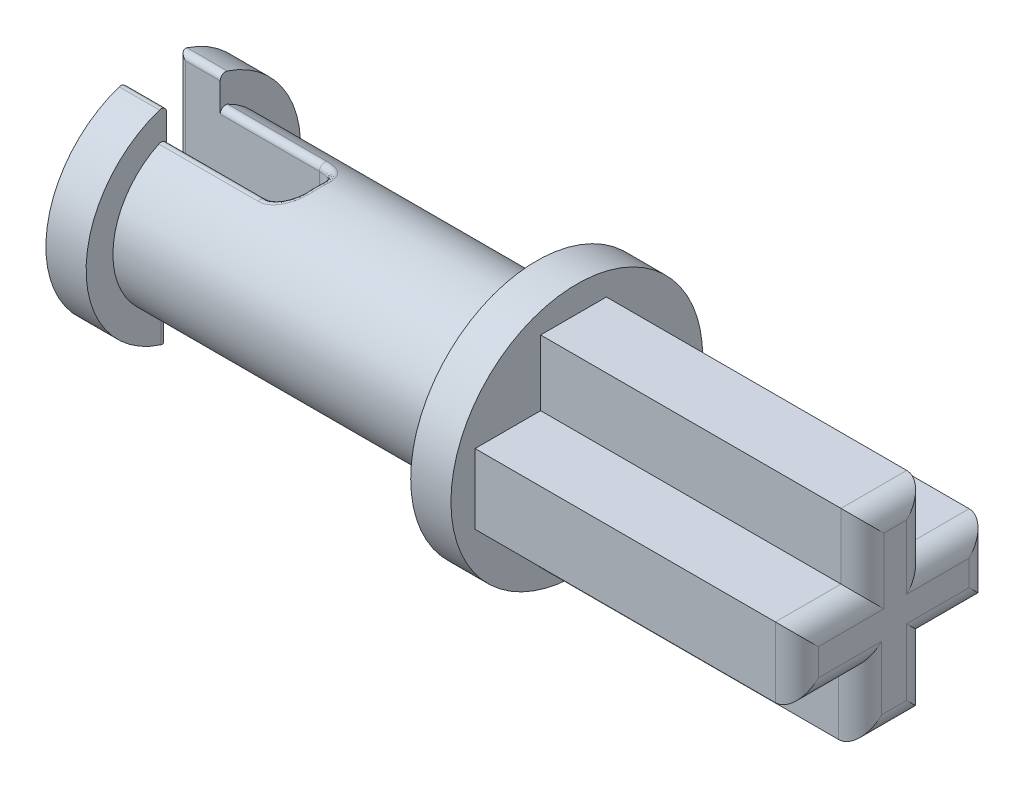
SolidWorks part; units mm, degrees
ref_plane "Front Plane" through (0, 0, 0) normal (0, 0, 1) x (1, 0, 0)
ref_plane "Top Plane" through (0, 0, 0) normal (0, 1, 0) x (1, 0, 0)
ref_plane "Right Plane" through (0, 0, 0) normal (1, 0, 0) x (0, 0, -1)
sketch "CircularBase" plane through (0, 0, 0) normal (0, 0, 1) x (1, 0, 0)
  line L0 (-5.0594, 0) -> (5.9, 0) construction
  line L1 (0, 0) -> (0, 0.5)
  line L2 (0, 0.5) -> (-2, 0.5)
  line L3 (-2, 0.5) -> (-2, 2)
  line L4 (-2, 2) -> (-1.25, 2)
  line L5 (-1.25, 2) -> (-1.25, 1.5)
  line L6 (-1.25, 1.5) -> (5.15, 1.5)
  line L7 (5.15, 1.5) -> (5.15, 2.3473)
  line L9 (5.9, 2.3473) -> (5.9, 0)
  line L11 (0, 0) -> (5.9, 0)
  line L12 (7.0797, 0) -> (14.1483, 0) construction
  line L13 (5.15, 2.3473) -> (5.9, 2.3473)
  dimension "D2" = 0.75
  dimension "D4" = 0.5
  dimension "D5" = 1.5
  dimension "D6" = 0.5
  dimension "D8" = 2
  dimension "D9" = 5.9
revolve "CircularBaseRevolve" add sketch "CircularBase" angle 360 about L12
ref_plane "BasePlane" through (-2, 0, 0) normal (-1, 0, 0) x (0, 0, 1)
sketch "NotchCutSketc" plane through (-2, 0, 0) normal (-1, 0, 0) x (0, 0, 1)
  line L0 (0, 2) -> (0, -2) construction
  line L1 (-0.5, 0) -> (-0.5, 1.9365)
  line L2 (-0.5, 1.9365) -> (0.5, 1.9365)
  line L3 (-0.5, 0) -> (-0.5, -1.9365)
  line L4 (-0.5, -1.9365) -> (0.5, -1.9365)
  line L5 (0.5, 0) -> (0.5, -1.9365)
  line L6 (0.5, 0) -> (0.5, 1.9365)
  circle A0 centre (0, 0) radius 2 construction
  circle A1 centre (0, 0) radius 0.5 construction
  circle A2 centre (0, 0) radius 0.5 construction
  point P15 (0, -1.9365)
  point P17 (0, 1.9365)
extrude "NotchCut" cut sketch "NotchCutSketc" against normal blind 3
fillet "InsideNotchFillet1" radius 0.4 1 edges at (1, 0, -0.5) type face fillet first side face at (-0.875, 0, -0.5) second side face at (1, 0, 0)
fillet "InsideNotchFillet2" radius 0.4 1 edges at (1, 0, 0.5) type face fillet first side face at (-0.875, 0, 0.5) second side face at (1, 0, 0.2021)
fillet "OutsideNotchFillet" radius 0.1 16 edges at (-2, 0, 0.5) (-2, 0, -0.5) (-0.325, -1.4142, -0.5) (0.915, -1.4594, -0.3465) (1, -1.5, 0) (0.8413, -1.4403, 0.419) (-0.325, 1.4142, 0.5) (0.915, 1.4594, 0.3465) (1, 1.5, 0) (0.8413, 1.4403, -0.419) (-1.625, 1.9365, 0.5) (-1.625, 1.9365, -0.5) (-1.625, -1.9365, -0.5) (-0.325, -1.4142, 0.5) (-0.325, 1.4142, -0.5) (-1.25, -1.6754, 0.5)
ref_plane "TopBasePlane" through (5.9, 0, 0) normal (1, 0, 0) x (0, 0, -1)
sketch "TopCircularBaseExtrudeSketch" plane through (5.9, 0, 0) normal (1, 0, 0) x (0, 0, -1)
  line L16 (-1.8975, -0.6644) -> (-1.8975, 0.6397)
  line L17 (-1.8975, 0.6397) -> (-0.6748, 0.6397)
  line L18 (0.5517, 1.8623) -> (-0.6748, 1.8623)
  line L19 (-0.6748, 1.8623) -> (-0.6748, 0.6397)
  line L20 (1.7152, -0.613) -> (1.7152, 0.6617)
  line L21 (1.7152, 0.6617) -> (0.5517, 0.6617)
  line L22 (0.5517, 1.8623) -> (0.5517, 0.6617)
  line L23 (1.7152, -0.613) -> (0.547, -0.613)
  line L24 (0.547, -1.851) -> (0.547, -0.613)
  line L25 (-1.8975, -0.6644) -> (-0.7166, -0.6644)
  line L26 (-0.7166, -1.851) -> (-0.7166, -0.6644)
  line L27 (0.547, -1.851) -> (-0.7166, -1.851)
  point P16 (1.7152, 0.0244)
extrude "TopCircularBaseExtrude" add sketch "TopCircularBaseExtrudeSketch" along normal blind 6
fillet "TopCircularBaseFillet" radius 0.4 12 edges at (11.9, 1.251, 0.6748) (11.9, 1.262, -0.5517) (11.9, 0.6397, 1.2862) (11.9, 0.6617, -1.1335) (11.9, 0.0244, -1.7152) (11.9, -0.613, -1.1311) (11.9, -1.232, -0.547) (11.9, -1.851, 0.0848) (11.9, -0.0124, 1.8975) (11.9, 1.8623, 0.0616) (11.9, -0.6644, 1.3071) (11.9, -1.2577, 0.7166)
fillet "TopCircularbaseSideFillet" [suppressed] radius 0.1
ref_plane "Plane1" [suppressed] through (0, -2.007, 0) normal (0, -1, 0) x (-1, 0, 0)
sketch "CircularTipSketch" [suppressed] plane through (0, -2.007, 0) normal (0, -1, 0) x (-1, 0, 0)
  line L0 (-6, 2.0033) -> (-6, -2.0033)
  line L1 (-6, -2.0033) -> (-6, -2.5355)
  line L2 (-6, -2.5355) -> (2.115, -2.5355)
  line L3 (2.115, -2.5355) -> (1.9623, 2.8509)
  line L4 (1.9623, 2.8509) -> (-6, 2.7898)
  line L5 (-6, 2.7898) -> (-6, 2.0033)
extrude "CircularTip" [suppressed] cut sketch "CircularTipSketch" against normal through all
ref_plane "Plane2" [suppressed] through (6, 0, 0) normal (-1, 0, 0) x (0, 0, 1)
mirror "Mirror2" [suppressed]
ref_plane "Plane3" [suppressed] through (0, 2.007, 0) normal (0, 1, 0) x (1, 0, 0)
sketch "BaseCutSketch" [suppressed] plane through (0, 2.007, 0) normal (0, 1, 0) x (1, 0, 0)
  line L0 (5.15, 2.5558) -> (5.15, -2.5)
  line L1 (5.15, -2.5) -> (-2.0426, -2.5)
  line L2 (-2.0426, -2.5) -> (-2.0426, 2.5558)
  line L3 (-2.0426, 2.5558) -> (5.15, 2.5558)
extrude "BaseCut" [suppressed] cut sketch "BaseCutSketch" against normal through all contours L3 L2 L1 L0
ref_plane "Plane4" [suppressed] through (13.8, 0, 0) normal (1, 0, 0) x (0, 0, -1)
sketch "NotchCutSketch" [suppressed] plane through (0, 0, 0) normal (0, 1, 0) x (1, 0, 0)
  line L7 (7.7505, 3.747) -> (7.7505, 0)
  line L14 (7.7505, 0) -> (10.818, 0) construction
  line L19 (7.7505, 0) -> (5.15, 0)
  line L20 (5.15, 2.5) -> (5.15, -2.5) construction
  line L21 (5.15, 0) -> (5.15, 4)
  line L22 (5.15, 4) -> (6.4505, 4)
  line L23 (6.4505, 4) -> (6.4505, 3.747)
  line L24 (6.4505, 3.747) -> (7.7505, 3.747)
  point P16 (7.1, 2.25)
  dimension "D1" = 1.3
  dimension "D2" = 4
revolve "CircularEvolveWithNotch" [suppressed] add sketch "NotchCutSketch" angle 360 about L14
ref_plane "Plane5" [suppressed] through (5.15, 0, 0) normal (-1, 0, 0) x (0, 0, 1)
sketch "CrossHoleCutSketch" [suppressed] plane through (5.15, 0, 0) normal (-1, 0, 0) x (0, 0, 1)
  line L0 (-0.8429, 0.8584) -> (-0.8429, 1.9149)
  line L1 (-0.6429, 2.1149) -> (0.6506, 2.1149)
  line L2 (0.8506, 1.9149) -> (0.8506, 0.8584)
  line L3 (0.8506, 0.8584) -> (1.9071, 0.8584)
  line L4 (-1.8994, 0.8584) -> (-0.8429, 0.8584)
  line L5 (-0.8429, -0.8427) -> (-1.8994, -0.8427)
  line L6 (-0.8429, -0.8427) -> (-0.8429, -1.8992)
  line L7 (-0.6429, -2.0992) -> (0.6506, -2.0992)
  line L8 (0.8506, -1.8992) -> (0.8506, -0.8427)
  line L9 (0.8506, -0.8427) -> (1.9071, -0.8427)
  line L10 (2.1071, -0.6427) -> (2.1071, 0.6584)
  line L11 (-2.0994, -0.6427) -> (-2.0994, 0.6584)
  arc A0 (-0.8429, 1.9149) -> (-0.6429, 2.1149) centre (-0.6429, 1.9149) cw
  arc A1 (0.8506, 1.9149) -> (0.6506, 2.1149) centre (0.6506, 1.9149) ccw
  arc A2 (1.9071, 0.8584) -> (2.1071, 0.6584) centre (1.9071, 0.6584) cw
  arc A3 (1.9071, -0.8427) -> (2.1071, -0.6427) centre (1.9071, -0.6427) ccw
  arc A4 (0.8506, -1.8992) -> (0.6506, -2.0992) centre (0.6506, -1.8992) cw
  arc A5 (-0.6429, -2.0992) -> (-0.8429, -1.8992) centre (-0.6429, -1.8992) cw
  arc A6 (-1.8994, -0.8427) -> (-2.0994, -0.6427) centre (-1.8994, -0.6427) cw
  arc A7 (-1.8994, 0.8584) -> (-2.0994, 0.6584) centre (-1.8994, 0.6584) ccw
extrude "CrossHoleCut" [suppressed] cut sketch "CrossHoleCutSketch" against normal through all
ref_plane "Plane11" [suppressed] through (7.7505, 0, 0) normal (1, 0, 0) x (0, 0, -1)
sketch "Sketch16" [suppressed] plane through (7.7505, 0, 0) normal (1, 0, 0) x (0, 0, -1)
  line L1 (0.8429, 0.8584) -> (0.8429, 1.9149)
  line L3 (-0.8506, 0.8584) -> (-1.9071, 0.8584)
  line L4 (-2.1071, 0.6584) -> (-2.1071, -0.6427)
  line L5 (-1.9071, -0.8427) -> (-0.8506, -0.8427)
  line L6 (-0.8506, -0.8427) -> (-0.8506, -1.8992)
  line L7 (0.8429, -1.8992) -> (0.8429, -0.8427)
  line L8 (0.8429, -0.8427) -> (1.8994, -0.8427)
  line L9 (2.0994, -0.6427) -> (2.0994, 0.7075)
  line L10 (0.8429, 0.8584) -> (1.8994, 0.8584)
  line L11 (-0.6506, -2.0992) -> (0.6429, -2.0992)
  line L12 (-0.8506, 0.8584) -> (-0.8506, 1.9149)
  line L13 (-0.6506, 2.1149) -> (0.6429, 2.1149)
  circle A0 centre (0, 0) radius 4
  arc A1 (-1.9071, -0.8427) -> (-2.1071, -0.6427) centre (-1.9071, -0.6427) cw
  arc A2 (-2.1071, 0.6584) -> (-1.9071, 0.8584) centre (-1.9071, 0.6584) cw
  arc A6 (1.8994, 0.8584) -> (2.0994, 0.7075) centre (1.8994, 0.6504) cw
  arc A7 (2.0994, -0.6427) -> (1.8994, -0.8427) centre (1.8994, -0.6427) cw
  arc A8 (0.8429, -1.8992) -> (0.6429, -2.0992) centre (0.6429, -1.8992) cw
  arc A9 (-0.8506, -1.8992) -> (-0.6506, -2.0992) centre (-0.6506, -1.8992) ccw
  arc A10 (-0.8506, 1.9149) -> (-0.6506, 2.1149) centre (-0.6506, 1.9149) cw
  arc A11 (0.8429, 1.9149) -> (0.6429, 2.1149) centre (0.6429, 1.9149) ccw
extrude "CircularCrossHolwCircle" [suppressed] add sketch "Sketch16" along normal blind 1.25
fillet "EdgesFillet" [suppressed] radius 0.1
fillet "Fillet2" [suppressed] radius 0.1
ref_plane "Plane6" [suppressed] through (0, 0, -2.0033) normal (0, 0, -1) x (-1, 0, 0)
sketch "Sketch1" [suppressed] plane through (0, 0, -2.0033) normal (0, 0, -1) x (-1, 0, 0)
  line L0 (-5.9, 2.5) -> (-5.9, -2.5)
  line L1 (-5.9, 2.5) -> (-5.9, -2.5) construction
  line L2 (-5.9, -2.5) -> (-13.8486, -2.5)
  line L3 (-13.8486, -2.5) -> (-13.8486, 2.5)
  line L4 (-13.8486, 2.5) -> (-5.9, 2.5)
extrude "RemovedMaterial" [suppressed] cut sketch "Sketch1" against normal through all
sketch "Sketch2" [suppressed] plane through (0, 0, -2.0033) normal (0, 0, -1) x (-1, 0, 0)
  line L1 (-11.5273, 0) -> (-12.3621, 0) construction
  line L2 (-5.15, 4.2) -> (-5.15, 0.25)
  line L3 (-5.15, 4.2) -> (-8.341, 4.2)
  line L4 (-8.341, 1.2482) -> (-11.5214, 1.2482)
  line L6 (-11.5214, 1.2482) -> (-11.5214, 0.25)
  line L8 (-8.341, 4.2) -> (-8.341, 1.2482)
  line L10 (-5.15, -2.5) -> (-5.15, 2.5) construction
  line L11 (-5.15, 0.25) -> (-11.5214, 0.25)
  dimension "D1" = 3.95
revolve "Revolve2" [suppressed] add sketch "Sketch2" angle 360 about L1
ref_plane "Plane8" [suppressed] through (5.9, 0, 0) normal (1, 0, 0) x (0, 0, -1)
sketch "Sketch13" [suppressed] plane through (5.9, 0, 0) normal (1, 0, 0) x (0, 0, -1)
  arc A0 (-1.8412, 1.6911) -> (-1.8412, -1.6911) centre (0, 0) ccw
  arc A2 (-1.8412, 1.6911) -> (-1.8412, -1.6911) centre (2.0033, 0) ccw
  dimension "D1" = 2.5
extrude "RemovedMaterial2" [suppressed] cut sketch "Sketch13" against normal through all
sketch "Sketch14" [suppressed] plane through (5.9, 0, 0) normal (1, 0, 0) x (0, 0, -1)
  line L0 (2.0033, -0.25) -> (2.0033, 0.25) construction
  circle A0 centre (2.0033, 0) radius 0.2516
ref_plane "ShellPlane" [suppressed] through (5.15, 0, 0) normal (-1, 0, 0) x (0, 0, 1)
sketch "ShellSketch" [suppressed] plane through (5.15, 0, 0) normal (-1, 0, 0) x (0, 0, 1)
  circle A0 centre (-2.0033, 0) radius 1.9017
extrude "ShellFeature" [suppressed] cut sketch "ShellSketch" against normal blind 1.6
ref_plane "Plane13" [suppressed] through (8.341, 0, 0) normal (1, 0, 0) x (0, 0, -1)
sketch "RemoveMaterialSketch3" [suppressed] plane through (8.341, 0, 0) normal (1, 0, 0) x (0, 0, -1)
  circle A0 centre (2.0033, 0) radius 1.2482
extrude "RemoveMaterial3" [suppressed] cut sketch "RemoveMaterialSketch3" along normal through all
sketch "Sketch21" [suppressed] plane through (8.341, 0, 0) normal (1, 0, 0) x (0, 0, -1)
  circle A0 centre (2.0033, 0) radius 2.4
  circle A1 centre (2.0033, 0) radius 2
  dimension "D1" = 4.8
  dimension "D2" = 4
extrude "CylindereExtrudeVertical" [suppressed] add sketch "Sketch21" along normal blind 2
sketch "ThroughHoleSketch" [suppressed] plane through (8.341, 0, 0) normal (1, 0, 0) x (0, 0, -1)
  circle A0 centre (2.0033, 0) radius 2
extrude "ThroughHole" [suppressed] cut sketch "ThroughHoleSketch" against normal through all
ref_plane "Plane14" [suppressed] through (5.15, 0, 0) normal (-1, 0, 0) x (0, 0, 1)
sketch "Sketch23" [suppressed] plane through (5.15, 0, 0) normal (-1, 0, 0) x (0, 0, 1)
  circle A0 centre (-2.0033, 0) radius 2.4
  dimension "D1" = 4.8
extrude "Cut-Extrude6" [suppressed] cut sketch "Sketch23" against normal blind 1.6
ref_plane "BisectingPlane" [suppressed] through (6.7455, 0, 0) normal (1, 0, 0) x (0, 0, -1)
sketch "Sketch24" [suppressed] plane through (6.7455, 0, 0) normal (1, 0, 0) x (0, 0, -1)
  line L0 (2.0033, 0) -> (2.0033, 3.4935) construction
  line L2 (3.5835, 3.5518) -> (3.5835, 8.4935)
  line L4 (2.0033, 9.1481) -> (2.0033, 10.1942) construction
  line L5 (2.0033, 9.1481) -> (2.0033, 3.5518)
  line L6 (2.0033, 3.5518) -> (3.5835, 3.5518)
  arc A0 (2.0033, 9.1481) -> (3.5835, 8.4935) centre (2.0033, 6.9132) cw
  point P7 (2.0033, 3.4935)
revolve "CylinderRevolve" [suppressed] add sketch "Sketch24" angle 360 about L4
sketch "Sketch25" [suppressed] plane through (6.7455, 0, 0) normal (1, 0, 0) x (0, 0, -1)
  line L0 (2.0033, 4.2) -> (2.0033, 10.2085) construction
  line L1 (3.5835, 8.4935) -> (0.423, 8.4935) construction
  arc A0 (3.5835, 3.8914) -> (0.423, 3.8914) centre (2.0033, 0) ccw construction
  circle A1 centre (2.0033, 8.4935) radius 1.5349
extrude "Boss-Extrude3" [suppressed] add sketch "Sketch25" against normal blind 7
sketch "Sketch27" [suppressed] plane through (6.7455, 0, 0) normal (1, 0, 0) x (0, 0, -1)
  line L0 (2.0033, 8.4935) -> (2.0033, 10.0284)
  line L1 (3.5835, 8.4935) -> (0.423, 8.4935) construction
  line L2 (2.0033, 8.4935) -> (0.423, 8.4935)
  line L3 (2.0033, 10.379) -> (2.0033, 10.0284) construction
  arc A0 (3.5376, 8.5382) -> (0.469, 8.5382) centre (2.0033, 8.4935) ccw construction
  arc A1 (0.423, 8.4935) -> (2.0033, 10.0284) centre (1.9586, 8.4935) cw
revolve "Revolve4" [suppressed] add sketch "Sketch27" angle 360 about L3
ref_plane "Plane17" [suppressed] through (-0.2545, 0, 0) normal (-1, 0, 0) x (0, 0, 1)
sketch "Sketch28" [suppressed] plane through (-0.2545, 0, 0) normal (-1, 0, 0) x (0, 0, 1)
  line L0 (-2.0033, 10.0284) -> (-2.0033, 6.9586) construction
  line L1 (-3.5382, 8.4935) -> (-0.4683, 8.4935) construction
  arc A0 (-3.5382, 8.4935) -> (-0.4683, 8.4935) centre (-2.0033, 8.4935) ccw construction
  circle A1 centre (-2.0033, 8.4935) radius 0.5026
extrude "SmallHoleInCylinder" [suppressed] cut sketch "Sketch28" against normal blind 3
ref_plane "Plane18" [suppressed] through (21.6, 0, 0) normal (1, 0, 0) x (0, 0, -1)
sketch "Sketch29" [suppressed] plane through (21.6, 0, 0) normal (1, 0, 0) x (0, 0, -1)
  line L7 (0.776, -2.675) -> (-1.1035, -2.675) construction
  line L8 (1.0733, 2.6336) -> (1.0733, 1.1385) construction
  line L9 (-1.0733, 2.6336) -> (-1.0733, 1.1201) construction
  line L10 (-1.0733, 2.6336) -> (1.0733, 2.652)
  line L11 (1.0733, 2.652) -> (1.0733, 1.1385)
  line L12 (1.0733, 1.1385) -> (2.4478, 1.1385)
  line L13 (2.4478, 1.1385) -> (2.4478, -1.1615)
  line L14 (2.4478, -1.1615) -> (1.0733, -1.1615)
  line L16 (1.0733, -2.675) -> (-1.1035, -2.675)
  line L17 (-1.1035, -2.675) -> (-1.1035, -1.1615)
  line L18 (-1.1035, -1.1615) -> (-2.4478, -1.1615)
  line L19 (-2.4478, -1.1615) -> (-2.4478, 1.1201)
  line L20 (-2.4478, 1.1201) -> (-1.0733, 1.1201)
  line L21 (-1.0733, 1.1201) -> (-1.0733, 2.6336)
  line L23 (1.0733, -1.1615) -> (1.0733, -2.675)
  circle A0 centre (0, 0) radius 3.45
  dimension "D1" = 6.9
  dimension "D3" = 0.775
  dimension "D2" = 2.3
extrude "Boss-Extrude5" [suppressed] add sketch "Sketch29" along normal blind 15.8 separate body
ref_plane "Plane19" [suppressed] through (0, 0, -2.0033) normal (0, 0, -1) x (-1, 0, 0)
sketch "Sketch30" [suppressed] plane through (0, 0, -2.0033) normal (0, 0, -1) x (-1, 0, 0)
  line L0 (-21.6, 3.4921) -> (-21.6, -3.45)
  line L1 (-21.6, 3.1156) -> (-21.6, -3.1156) construction
  line L2 (-21.6, -3.45) -> (-21.6, 3.45) construction
  line L3 (-21.6, -3.45) -> (9.8373, -3.45)
  line L4 (9.8373, -3.45) -> (9.8373, 3.4921)
  line L5 (9.8373, 3.4921) -> (-21.6, 3.4921)
extrude "Cut-Extrude7" [suppressed] cut sketch "Sketch30" against normal through all
sketch "Sketch31" [suppressed] plane through (21.6, 0, 0) normal (1, 0, 0) x (0, 0, -1)
  line L0 (0, -3.485) -> (0, 0) construction
  line L1 (0, 0) -> (2.3068, 0) construction
  line L3 (-2.6444, 2.1051) -> (-2.7334, 2.1051)
  line L5 (-2.6444, -2.1051) -> (-2.7334, -2.1051)
  line L7 (2.6444, -2.1051) -> (2.7334, -2.1051)
  line L8 (2.6444, 2.1051) -> (2.7334, 2.1051)
  circle A0 centre (0, 0) radius 3.45 construction
  arc A1 (-2.7334, 2.1051) -> (-1.8163, 2.9332) centre (-0.5362, 0.5938) cw
  arc A2 (-2.7334, -2.1051) -> (-1.8163, -2.9332) centre (-0.5362, -0.5938) ccw
  arc A3 (2.7334, -2.1051) -> (1.8163, -2.9332) centre (0.5362, -0.5938) cw
  arc A4 (2.7334, 2.1051) -> (1.8163, 2.9332) centre (0.5362, 0.5938) ccw
  arc A5 (-2.6444, 2.1051) -> (-1.8163, 2.9332) centre (-2.6889, 2.9777) ccw
  arc A6 (2.6444, 2.1051) -> (1.8163, 2.9332) centre (2.6889, 2.9777) cw
  arc A7 (-2.6444, -2.1051) -> (-1.8163, -2.9332) centre (-2.6889, -2.9777) cw
  arc A8 (2.6444, -2.1051) -> (1.8163, -2.9332) centre (2.6889, -2.9777) ccw
extrude "Cut-Extrude8" [suppressed] cut sketch "Sketch31" along normal through all
fillet "Fillet3" [suppressed] radius 0.4
